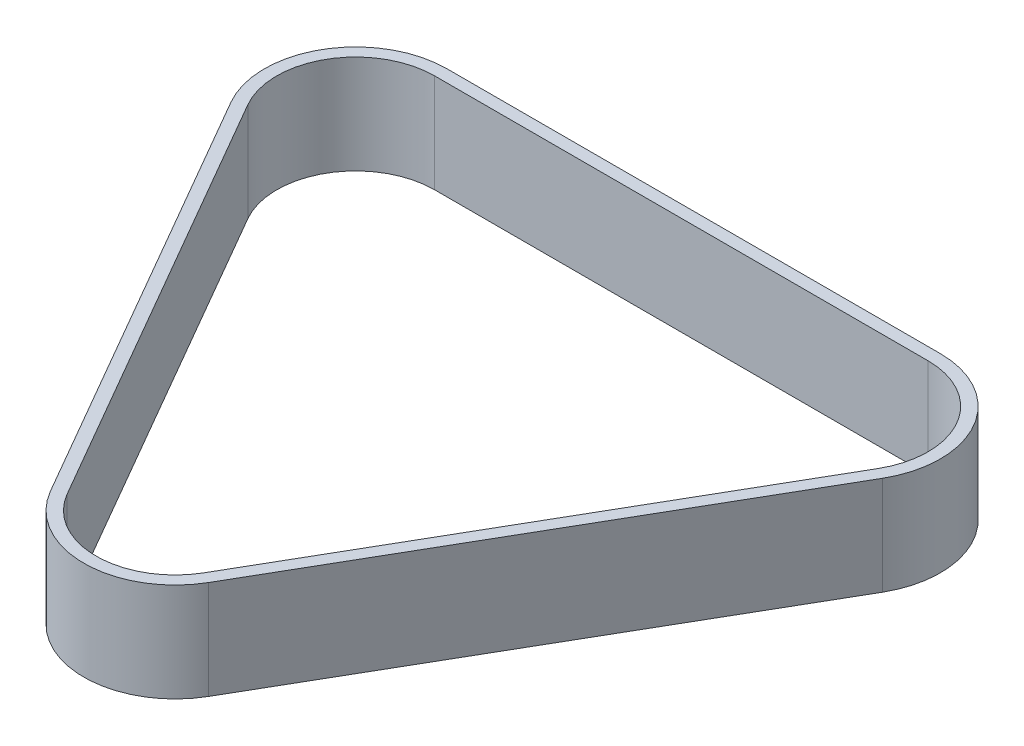
SolidWorks part; units mm, degrees
ref_plane "Front Plane" through (0, 0, 0) normal (0, 0, 1) x (1, 0, 0)
ref_plane "Top Plane" through (0, 0, 0) normal (0, 1, 0) x (1, 0, 0)
ref_plane "Right Plane" through (0, 0, 0) normal (1, 0, 0) x (0, 0, -1)
sketch "Sketch1" plane through (0, 0, 0) normal (0, 1, 0) x (1, 0, 0)
  line L0 (0, 0) -> (100, 0)
  line L1 (100, 0) -> (50, -86.6025)
  line L2 (50, -86.6025) -> (0, 0)
  line L3 (-13.8564, -8) -> (36.1436, -94.6025)
  line L4 (113.8564, -8) -> (63.8564, -94.6025)
  line L5 (100, 16) -> (0, 16)
  line L6 (100, 18.5) -> (0, 18.5)
  line L7 (-16.0215, -9.25) -> (33.9785, -95.8525)
  line L8 (66.0215, -95.8525) -> (116.0215, -9.25)
  circle A0 centre (100, 0) radius 16
  circle A1 centre (50, -86.6025) radius 16
  circle A2 centre (0, 0) radius 16
  circle A5 centre (100, 0) radius 18.5
  circle A6 centre (0, 0) radius 18.5
  circle A7 centre (50, -86.6025) radius 18.5
  dimension "D2" = 32
  dimension "D3" = 37
  dimension "D1" = 100
extrude "Boss-Extrude1" add sketch "Sketch1" along normal blind 20 contours A7 L3 A6 L7 | A7 L4 A1 L3 | A7 L8 A5 L4 | L4 A5 L5 A0 | A6 L5 A5 L6 | L5 A6 L3 A2 region at (-14.2403, 0, -8.2217) region at (50, 0, -17.285) region at (10.0307, 0, 51.9438) region at (95.3064, 0, -17.436) region at (33.4634, 0, 90.788) region at (89.9693, 0, 51.9438)
